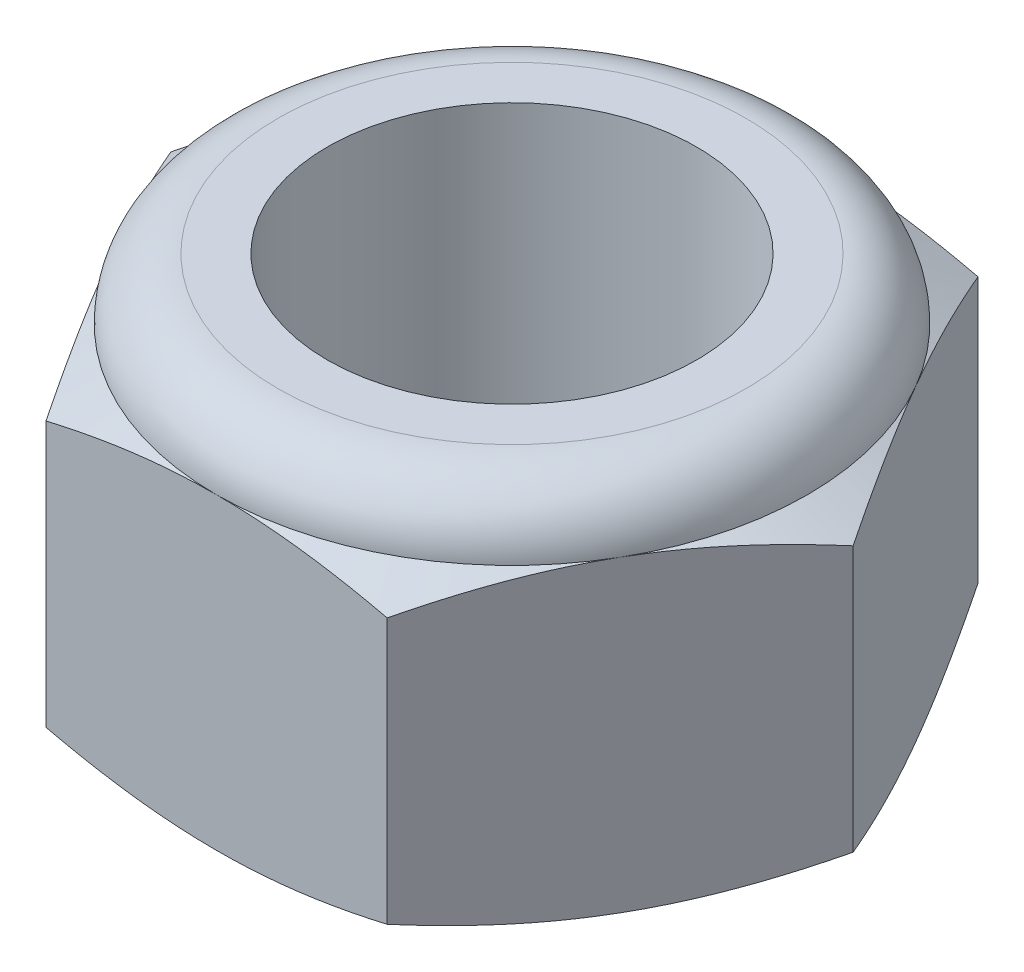
SolidWorks part; units mm, degrees
material "Stainless Steel (ferritic)"
ref_plane "Front" through (0, 0, 0) normal (0, 0, 1) x (1, 0, 0)
ref_plane "Top" through (0, 0, 0) normal (0, 1, 0) x (1, 0, 0)
ref_plane "Right" through (0, 0, 0) normal (1, 0, 0) x (0, 0, -1)
sketch "Sketch1" plane through (0, 0, 0) normal (0, 1, 0) x (1, 0, 0)
  line L1 (2.3094, 4) -> (-2.3094, 4)
  line L2 (-2.3094, 4) -> (-4.6188, 0)
  line L3 (-4.6188, 0) -> (-2.3094, -4)
  line L4 (-2.3094, -4) -> (2.3094, -4)
  line L5 (2.3094, -4) -> (4.6188, 0)
  line L6 (4.6188, 0) -> (2.3094, 4)
  circle A0 centre (0, 0) radius 4 construction
  circle A1 centre (0, 0) radius 2.5
  dimension "D2" = 5
  dimension "D1" = 8
extrude "Boss-Extrude1" add sketch "Sketch1" along normal blind 4.17
sketch "Sketch2" plane through (0, 4.17, 0) normal (0, 1, 0) x (1, 0, 0)
  line L0 (-2.3094, 4) -> (-4.6188, 0) construction
  circle A0 centre (0, 0) radius 4
  circle A1 centre (0, 0) radius 2.5 construction
  circle A2 centre (0, 0) radius 2.5
extrude "Boss-Extrude2" add sketch "Sketch2" along normal blind 0.83
fillet "Fillet1" radius 0.83 1 edges at (0, 5, 4)
sketch "Sketch3" plane through (0, 0, 0) normal (0, 0, 1) x (1, 0, 0)
  line L0 (-4, 4.17) -> (-4.6188, 4.17)
  line L1 (-4.6188, 4.17) -> (-4.6188, 3.8814)
  line L2 (-4.6188, 4.17) -> (-4.6188, 0) construction
  line L3 (-4.6188, 3.8814) -> (-4, 4.17)
  line L4 (-4.6188, 2.085) -> (-2.3094, 2.085) construction
  line L5 (-2.3094, 4.17) -> (-2.3094, 0) construction
  line L6 (-4.6188, 0.2886) -> (-4, 0)
  line L7 (-4.6188, 0) -> (-4.6188, 0.2886)
  line L8 (-4, 0) -> (-4.6188, 0)
  dimension "D1" = 25
sketch "Sketch4" plane through (0, 0, 0) normal (0, 0, 1) x (1, 0, 0)
  line L0 (0, 0) -> (0, 5.3922) construction
  line L1 (-2.3094, 0) -> (2.3094, 0) construction
revolve "Cut-Revolve1" cut sketch "Sketch3" angle 360 about L0
